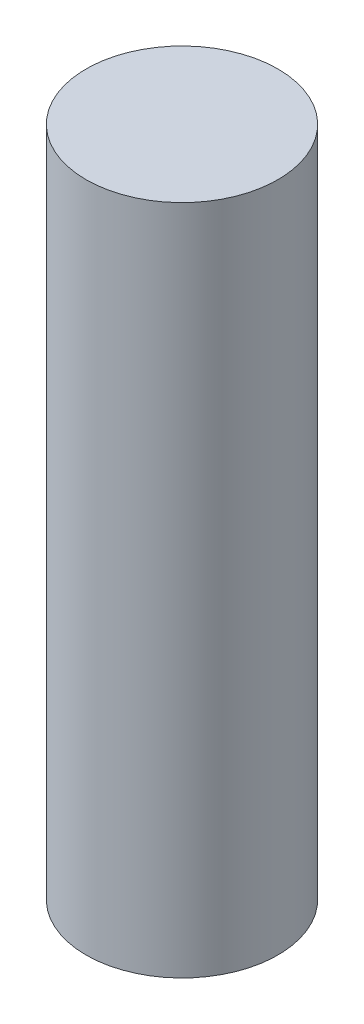
SolidWorks part; units mm, degrees
ref_plane "Front Plane" through (0, 0, 0) normal (0, 0, 1) x (1, 0, 0)
ref_plane "Top Plane" through (0, 0, 0) normal (0, 1, 0) x (1, 0, 0)
ref_plane "Right Plane" through (0, 0, 0) normal (1, 0, 0) x (0, 0, -1)
sketch "Sketch1" plane through (0, 0, 0) normal (0, 1, 0) x (1, 0, 0)
  circle A0 centre (0, 0) radius 5
  dimension "D1" = 10
extrude "Boss-Extrude1" add sketch "Sketch1" along normal blind 35
sketch "Sketch2" plane through (0, 0, 0) normal (0, -1, 0) x (1, 0, 0)
  line L0 (0, -2.5) -> (0, 2) construction
  line L1 (-1.5, 2) -> (1.5, 2)
  arc A0 (-1.5, 2) -> (1.5, 2) centre (0, 0) ccw
  dimension "D1" = 5
  dimension "D2" = 4.5
extrude "Cut-Extrude1" cut sketch "Sketch2" against normal blind 22
sketch "Sketch3" plane through (0, 0, 0) normal (0, -1, 0) x (1, 0, 0)
  circle A0 centre (0, 0) radius 2.5
  dimension "D1" = 5
extrude "Cut-Extrude2" cut sketch "Sketch3" against normal blind 4
